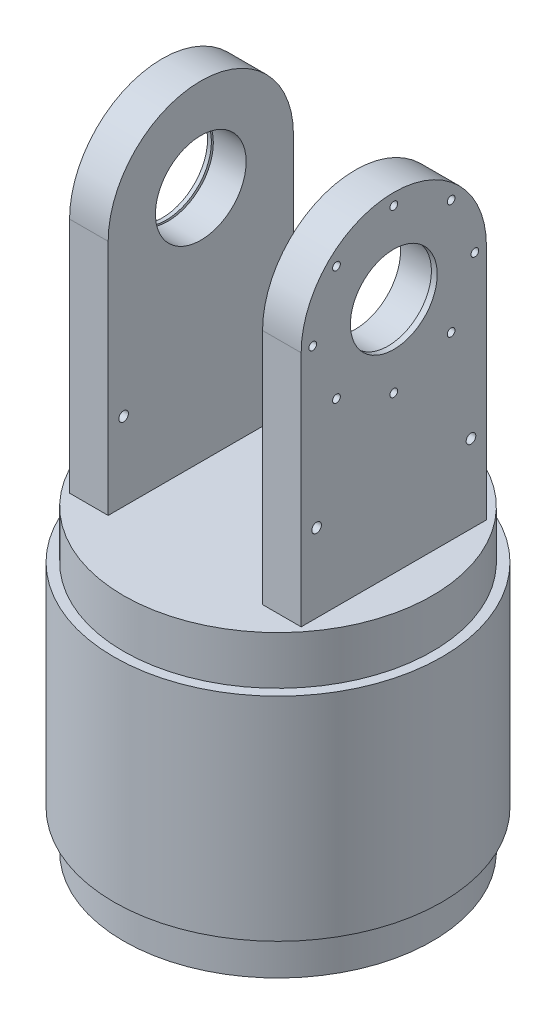
SolidWorks part; units mm, degrees
ref_plane "Front Plane" through (0, 0, 0) normal (0, 0, 1) x (1, 0, 0)
ref_plane "Top Plane" through (0, 0, 0) normal (0, 1, 0) x (1, 0, 0)
ref_plane "Right Plane" through (0, 0, 0) normal (1, 0, 0) x (0, 0, -1)
sketch "Sketch1" plane through (0, 0, 0) normal (0, 1, 0) x (1, 0, 0)
  circle A0 centre (0, 0) radius 85
  circle A1 centre (0, 0) radius 80
  circle A2 centre (0, 0) radius 75
  dimension "D1" = 170
  dimension "D2" = 160
  dimension "D3" = 150
extrude "Boss-Extrude1" add sketch "Sketch1" along normal blind 150 contours A1 A2 | A0 A1 region at (-82.5958, 0, 0) region at (-77.7373, 0, 0)
extrude "Cut-Extrude1" cut sketch "Sketch1<4>" along normal blind 155 contours A1 A2 region at (-77.7373, 0, 0)
sketch "Sketch1<4>" plane through (0, 0, 0) normal (0, 1, 0) x (1, 0, 0) same geometry as "Sketch1"
ref_plane "Plane1" through (0, 150, 0) normal (0, 1, 0) x (1, 0, 0)
sketch "Sketch2" plane through (0, 150, 0) normal (0, 1, 0) x (1, 0, 0)
  line L0 (0, 0) -> (136.3125, 0) construction
  line L1 (0, 0) -> (-96.2439, 0) construction
  line L3 (40, 48) -> (60, 48)
  line L4 (40, 48) -> (40, -48)
  line L5 (40, -48) -> (60, -48)
  line L6 (60, 48) -> (60, -48)
  line L7 (40, 48) -> (60, -48) construction
  line L8 (40, -48) -> (60, 48) construction
  line L9 (-60, 48) -> (-40, 48)
  line L10 (-60, 48) -> (-60, -48)
  line L11 (-60, -48) -> (-40, -48)
  line L12 (-40, 48) -> (-40, -48)
  line L13 (-60, 48) -> (-40, -48) construction
  line L14 (-60, -48) -> (-40, 48) construction
  circle A0 centre (0, 0) radius 40
  circle A1 centre (0, 0) radius 80
  point P3 (50, 0)
  point P6 (-50, 0)
  point P7 (50, 0)
  point P12 (-50, 0)
  circle M7 centre (0, 0) radius 85
  dimension "D1" = 80
  dimension "D8" = 160
  dimension "D2" = 50
  dimension "D3" = 50
  dimension "D4" = 20
  dimension "D5" = 96
  dimension "D6" = 20
  dimension "D7" = 96
extrude "Boss-Extrude3" add sketch "Sketch2" along normal blind 5 contours A1 L12 A0 L11 L10 L9 L3 L6 L5 L4 | L6 L3 L4 L5 | A0 M7 | M7 | L12 L9 L10 L11 region at (-50, 150, 0) region at (0, 150, 0) region at (50, 150, 0) region at (-77.7373, 150, 0) region at (-82.5958, 150, 0)
extrude "Boss-Extrude4" add sketch "Sketch2<3>" along normal blind 176 contours L6 L3 L4 L5 region at (50, 150, 0)
sketch "Sketch2<3>" plane through (0, 150, 0) normal (0, 1, 0) x (1, 0, 0) same geometry as "Sketch2"
extrude "Boss-Extrude5" add sketch "Sketch2<4>" along normal blind 176 contours L12 L9 L10 L11 region at (-50, 150, 0)
sketch "Sketch2<4>" plane through (0, 150, 0) normal (0, 1, 0) x (1, 0, 0) same geometry as "Sketch2"
ref_plane "Plane2" through (60, 0, 0) normal (1, 0, 0) x (0, 0, -1)
sketch "Sketch3" plane through (60, 0, 0) normal (1, 0, 0) x (0, 0, -1)
  line L0 (0, 128.5062) -> (0, 336.1653) construction
  circle A0 centre (0, 278) radius 30
  circle A1 centre (0, 278) radius 23.5
  circle A2 centre (0, 278) radius 22.5
  point P3 (0, 155)
  point P4 (0, 278)
  dimension "D2" = 60
  dimension "D3" = 47
  dimension "D4" = 45
  dimension "D1" = 123
extrude "Cut-Extrude3" cut sketch "Sketch3" against normal blind 90 contours A1 L0 | A2 L0 | L0 A2 | A1 region at (60, 278, 22.9745) region at (60, 278, 9.5493) region at (60, 278, -9.5493)
extrude "Cut-Extrude4" cut sketch "Sketch3<3>" against normal blind 120 contours A2 L0 | L0 A2 | L0 A1 A2 | A1 L0 A2 region at (60, 278, 22.9745) region at (60, 255, -0.5255) region at (60, 278, 9.5493) region at (60, 278, -9.5493)
sketch "Sketch3<3>" plane through (60, 0, 0) normal (1, 0, 0) x (0, 0, -1) same geometry as "Sketch3"
sketch "Sketch4" plane through (60, 0, 0) normal (1, 0, 0) x (0, 0, -1)
  line L3 (-48, 230) -> (48, 230)
  line L4 (-48, 230) -> (-48, 326)
  line L5 (-48, 326) -> (48, 326)
  line L6 (48, 230) -> (48, 326)
  line L7 (-48, 230) -> (48, 326) construction
  line L8 (-48, 326) -> (48, 230) construction
  arc A0 (48, 278) -> (-48, 278) centre (0, 278) ccw
extrude "Cut-Extrude5" cut sketch "Sketch4" against normal blind 20 contours L5 L4 | L6 L5 region at (60, 315.2783, 37.2783) region at (60, 315.2783, -37.2783)
ref_plane "Plane3" through (-60, 0, 0) normal (-1, 0, 0) x (0, 0, 1)
sketch "Sketch5" plane through (-60, 0, 0) normal (-1, 0, 0) x (0, 0, 1)
  line L0 (48, 326) -> (48, 155) construction
  line L1 (-48, 326) -> (-48, 155) construction
  line L3 (-48, 230) -> (48, 230)
  line L4 (-48, 230) -> (-48, 326)
  line L5 (-48, 326) -> (48, 326)
  line L6 (48, 230) -> (48, 326)
  line L7 (-48, 230) -> (48, 326) construction
  line L8 (-48, 326) -> (48, 230) construction
  arc A0 (48, 278) -> (-48, 278) centre (0, 278) ccw
extrude "Cut-Extrude6" cut sketch "Sketch5" against normal blind 20 contours A0 L5 L4 | A0 L6 L5 region at (-60, 315.2783, -37.2783) region at (-60, 315.2783, 37.2783)
sketch "Sketch6" plane through (60, 0, 0) normal (1, 0, 0) x (0, 0, -1)
  line L0 (0, 278) -> (0, 342.1182) construction
  circle A0 centre (0, 320) radius 2
  circle A8 centre (29.6985, 307.6985) radius 2
  circle A9 centre (42, 278) radius 2
  circle A10 centre (29.6985, 248.3015) radius 2
  circle A11 centre (0, 236) radius 2
  circle A12 centre (-29.6985, 248.3015) radius 2
  circle A13 centre (-42, 278) radius 2
  circle A14 centre (-29.6985, 307.6985) radius 2
  point P4 (0, 320)
  point P23 (0, 278)
  dimension "D2" = 4
  dimension "D1" = 42
  dimension "D3" = 8
extrude "Cut-Extrude7" cut sketch "Sketch6" against normal blind 20 contours L0 A0 | A0 L0 | A11 | A10 | A12 | A13 | A9 | A8 | A14 region at (60, 320, 0.8488) region at (60, 320, -0.8488) region at (60, 307.6985, -29.6985) region at (60, 278, -42) region at (60, 248.3015, -29.6985) region at (60, 236, 0) region at (60, 248.3015, 29.6985) region at (60, 278, 42) region at (60, 307.6985, 29.6985)
ref_plane "Plane4" through (0, 0, 48) normal (0, 0, 1) x (1, 0, 0)
sketch "Sketch11" plane through (60, 0, 0) normal (1, 0, 0) x (0, 0, -1)
  line L0 (0, 126.6824) -> (0, 281.1109) construction
  line L2 (-82.0917, 195.5) -> (103.4529, 195.5) construction
  circle A0 centre (-40, 195.5) radius 2.5
  circle A1 centre (40, 195.5) radius 2.5
  point P3 (0, 155)
  point P4 (0, 195.5)
  point P9 (40, 195.5)
  point P10 (-40, 195.5)
  dimension "D4" = 5
  dimension "D5" = 5
  dimension "D1" = 40.5
  dimension "D2" = 40
  dimension "D3" = 40
extrude "Cut-Extrude10" cut sketch "Sketch11" against normal blind 131
extrude "Boss-Extrude6" add sketch "Sketch1<7>" along normal blind 155 contours A1 A2 region at (-77.7373, 0, 0)
sketch "Sketch1<7>" plane through (0, 0, 0) normal (0, 1, 0) x (1, 0, 0) same geometry as "Sketch1"
extrude "Cut-Extrude12" cut sketch "Sketch1<10>" against normal blind 10 and the other way blind 20 contours A0 A1 region at (-82.5958, 0, 0)
sketch "Sketch1<10>" plane through (0, 0, 0) normal (0, 1, 0) x (1, 0, 0) same geometry as "Sketch1"
ref_plane "Plane5" through (0, 155, 0) normal (0, 1, 0) x (1, 0, 0)
sketch "Sketch12" plane through (0, 155, 0) normal (0, 1, 0) x (1, 0, 0)
  circle A0 centre (0, 0) radius 85
  circle A1 centre (0, 0) radius 80
  circle A2 centre (0, 0) radius 75
  dimension "D1" = 170
  dimension "D2" = 160
  dimension "D3" = 150
extrude "Cut-Extrude13" cut sketch "Sketch12" against normal blind 25 contours A0 A1 region at (-82.5958, 155, 0)
extrude "Boss-Extrude7" add sketch "Sketch1<11>" along normal blind 5 contours A2 region at (0, 0, 0)
sketch "Sketch1<11>" plane through (0, 0, 0) normal (0, 1, 0) x (1, 0, 0) same geometry as "Sketch1"
sketch "Sketch13" plane through (0, 0, 0) normal (0, 1, 0) x (1, 0, 0)
  line L0 (0, 0) -> (0, -60.2525) construction
  point P3 (0, -14.25)
  point P7 (-12.3409, 7.125)
  point P8 (12.3409, 7.125)
  point P9 (0, 0)
  dimension "D1" = 14.25
  dimension "D2" = 3
hole_wizard "Ø5.0mm Dowel Hole1" positions "Sketch14" profile "Sketch15" hole size "Ø5.0" standard "ISO"
sketch "Sketch14" plane through (0, 0, 0) normal (0, -1, 0) x (-1, 0, 0)
  point P0 (12.3409, 7.125)
  point P3 (-12.3409, 7.125)
  point P6 (0, -14.25)
sketch "Sketch15" plane through (-12.3409, 0, -7.125) normal (1, 0, 0) x (0, 0, -1)
  line L0 (0, 0) -> (0, 6.5022)
  line L1 (0, 6.5022) -> (2.5, 5)
  line L2 (2.5, 5) -> (2.5, 0.025)
  line L3 (2.5, 0.025) -> (2.525, 0)
  line L5 (2.525, 0) -> (0, 0)
  line L6 (-2.5, 0.025) -> (-2.525, 0) construction
  line L10 (0, 6.5022) -> (-2.5, 5) construction
  line L11 (0, -6.35) -> (0, 107.95) construction
  dimension "Hole Dia." = 5
  dimension "Hole Depth" = 5
  dimension "Near C'Sink Dia." = 5.05
  dimension "Near C'Sink Angle" = 90
  dimension "Drill Angle" = 118
extrude "Boss-Extrude8" add sketch "Sketch3<4>" against normal blind 3 contours L0 A1 A2 | A1 L0 A2 region at (60, 278, 22.9745) region at (60, 255, -0.5255)
sketch "Sketch3<4>" plane through (60, 0, 0) normal (1, 0, 0) x (0, 0, -1) same geometry as "Sketch3"
ref_plane "Plane6" through (-57, 0, 0) normal (-1, 0, 0) x (0, 0, 1)
sketch "Sketch16" plane through (-57, 0, 0) normal (-1, 0, 0) x (0, 0, 1)
  circle A0 centre (0, 278) radius 25
  dimension "D1" = 50
extrude "Cut-Extrude14" cut sketch "Sketch16" along normal blind 1
